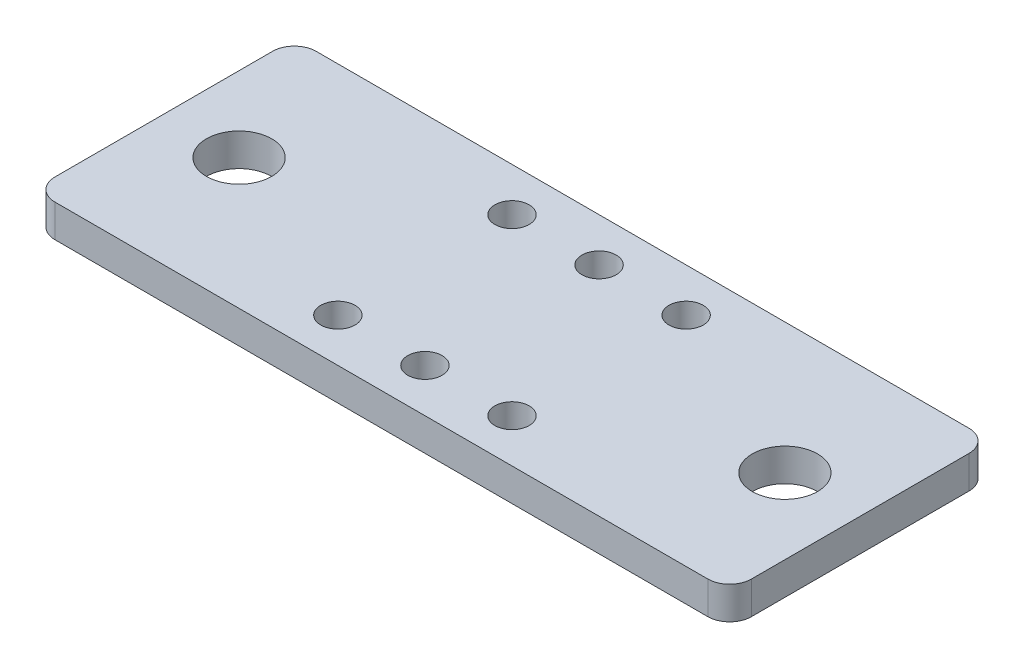
SolidWorks part; units mm, degrees
material "5052-H38, Barre (SS)"
ref_plane "Plan de face" through (0, 0, 0) normal (0, 0, 1) x (1, 0, 0)
ref_plane "Plan de dessus" through (0, 0, 0) normal (0, 1, 0) x (1, 0, 0)
ref_plane "Plan de droite" through (0, 0, 0) normal (1, 0, 0) x (0, 0, -1)
sketch "Esquisse1" plane through (0, 0, 0) normal (0, 1, 0) x (1, 0, 0)
  line L1 (50.8, 19.05) -> (-50.8, 19.05)
  line L2 (50.8, 19.05) -> (50.8, -19.05)
  line L3 (50.8, -19.05) -> (-50.8, -19.05)
  line L4 (-50.8, 19.05) -> (-50.8, -19.05)
  line L5 (50.8, 19.05) -> (-50.8, -19.05) construction
  line L6 (50.8, -19.05) -> (-50.8, 19.05) construction
  point P0 (0, 0)
  dimension "D1" = 101.6
  dimension "D2" = 38.1
base flange "Tôle de base pliée1" sketch "Esquisse1" thickness 4.76 reverse thickness direction no parameters "D1"=0.3125
sketch "Esquisse13" plane through (0, 0, 0) normal (0, 1, 0) x (1, 0, 0)
  line L0 (0, 19.05) -> (0, -19.05) construction
  line L1 (50.8, 19.05) -> (-50.8, 19.05) construction
  line L3 (-50.8, 0) -> (50.8, 0) construction
  line L4 (-50.8, 19.05) -> (-50.8, -19.05) construction
  line L5 (50.8, -19.05) -> (50.8, 19.05) construction
  line L7 (-50.8, -19.05) -> (50.8, -19.05) construction
  circle A0 centre (-39.8145, 0) radius 4.7625
  circle A1 centre (39.8145, 0) radius 4.7625
  dimension "D1" = 9.525
  dimension "D2" = 79.629
extrude "Enlèv. mat.-Extru.3" cut sketch "Esquisse13" against normal through all normal cut yes
hole_wizard "Diamètre du perçage Ø5.0 (5)1" positions "Esquisse15" profile "Esquisse14" hole size "Ø5.0" standard "Ansi Metric" end condition through all
sketch "Esquisse15" plane through (0, 0, 0) normal (0, 1, 0) x (1, 0, 0)
  line L0 (-12.7, 12.7) -> (12.7, 12.7) construction
  line L2 (0, 0) -> (0, 12.7) construction
  line L4 (50.8, 19.05) -> (-50.8, 19.05) construction
  point P0 (-12.7, 12.7)
  point P2 (0, 12.7)
  point P4 (12.7, 12.7)
  dimension "D1" = 6.35
  dimension "D2" = 25.4
sketch "Esquisse14" plane through (-12.7, 0, -12.7) normal (1, 0, 0) x (0, 0, 1)
  line L0 (0, 0) -> (0, 4.76)
  line L1 (0, 4.76) -> (2.5, 4.76)
  line L2 (2.5, 4.76) -> (2.5, 0)
  line L5 (2.5, 0) -> (0, 0)
  line L11 (0, -6.35) -> (0, 107.95) construction
  dimension "Diamètre du perçage jusqu'au prochain" = 5
  dimension "Profondeur du perçage jusqu'au prochain" = 4.76
pattern_linear "Répétition linéaire1" count 2 spacing 25.4 along (0, 0, 1) of "Diamètre du perçage Ø5.0 (5)1"
fillet "Congé2" radius 3.175 4 edges at (50.8, -2.38, -19.05) (50.8, -2.38, 19.05) (-50.8, -2.38, -19.05) (-50.8, -2.38, 19.05)
sketch "Lignes de pliage1" [suppressed] plane through (0, 0, 0) normal (0, 1, 0) x (1, 0, 0)
sketch "Cube de visualisation1" [suppressed] plane through (0, 0, 0) normal (0, 1, 0) x (1, 0, 0)
sheet metal parameters "Tôlerie1" thickness 4.76 parameters "D1"=0.3125
flat pattern "Etat déplié1" [suppressed]
sketch "Lignes de pliage2" plane through (0, 0, 0) normal (0, 1, 0) x (1, 0, 0)
sketch3d "Cube de visualisation2" [suppressed]
  line L0 (50.8, 19.05, 0) -> (-50.8, 19.05, 0) construction
  line L1 (50.8, -19.05, 0) -> (-50.8, -19.05, 0) construction
  line L2 (50.8, 19.05, 0) -> (50.8, -19.05, 0) construction
  line L3 (-50.8, 19.05, 0) -> (-50.8, -19.05, 0) construction
sheet metal parameters "Tôlerie5" thickness 4.76 parameters "D1"=0.3125
flat pattern "Etat déplié1"
sketch "Lignes de pliage2" plane through (0, 0, 0) normal (0, 1, 0) x (1, 0, 0)
sketch3d "Cube de visualisation2" [suppressed]
  line L0 (50.8, 19.05, 0) -> (-50.8, 19.05, 0) construction
  line L1 (50.8, -19.05, 0) -> (-50.8, -19.05, 0) construction
  line L2 (50.8, 19.05, 0) -> (50.8, -19.05, 0) construction
  line L3 (-50.8, 19.05, 0) -> (-50.8, -19.05, 0) construction
sheet metal parameters "Tôlerie6" thickness 4.76 parameters "D1"=0.3125
flat pattern "Etat déplié1"
sketch "Lignes de pliage2" plane through (0, 0, 0) normal (0, 1, 0) x (1, 0, 0)
  line L0 (28.9822, -69.85) -> (28.9822, -31.75) construction
  line L1 (-28.9822, -31.75) -> (-28.9822, -69.85) construction
  line L2 (28.9822, -69.85) -> (28.9822, -31.75) construction
  line L3 (-28.9822, -31.75) -> (-28.9822, -69.85) construction
sketch3d "Cube de visualisation2" [suppressed]
  line L0 (-51.0244, -69.85, 0) -> (51.0244, -69.85, 0) construction
  line L1 (-51.0244, 19.05, 0) -> (51.0244, 19.05, 0) construction
  line L2 (-51.0244, -69.85, 0) -> (-51.0244, 19.05, 0) construction
  line L3 (51.0244, -69.85, 0) -> (51.0244, 19.05, 0) construction
sheet metal parameters "Tôlerie7" thickness 4.76 parameters "D1"=0.3125
flat pattern "Etat déplié1"
sketch "Lignes de pliage2" plane through (0, 0, 0) normal (0, 1, 0) x (1, 0, 0)
sketch3d "Cube de visualisation2" [suppressed]
  line L0 (50.8, 19.05, 0) -> (-50.8, 19.05, 0) construction
  line L1 (50.8, -19.05, 0) -> (-50.8, -19.05, 0) construction
  line L2 (50.8, 19.05, 0) -> (50.8, -19.05, 0) construction
  line L3 (-50.8, 19.05, 0) -> (-50.8, -19.05, 0) construction
